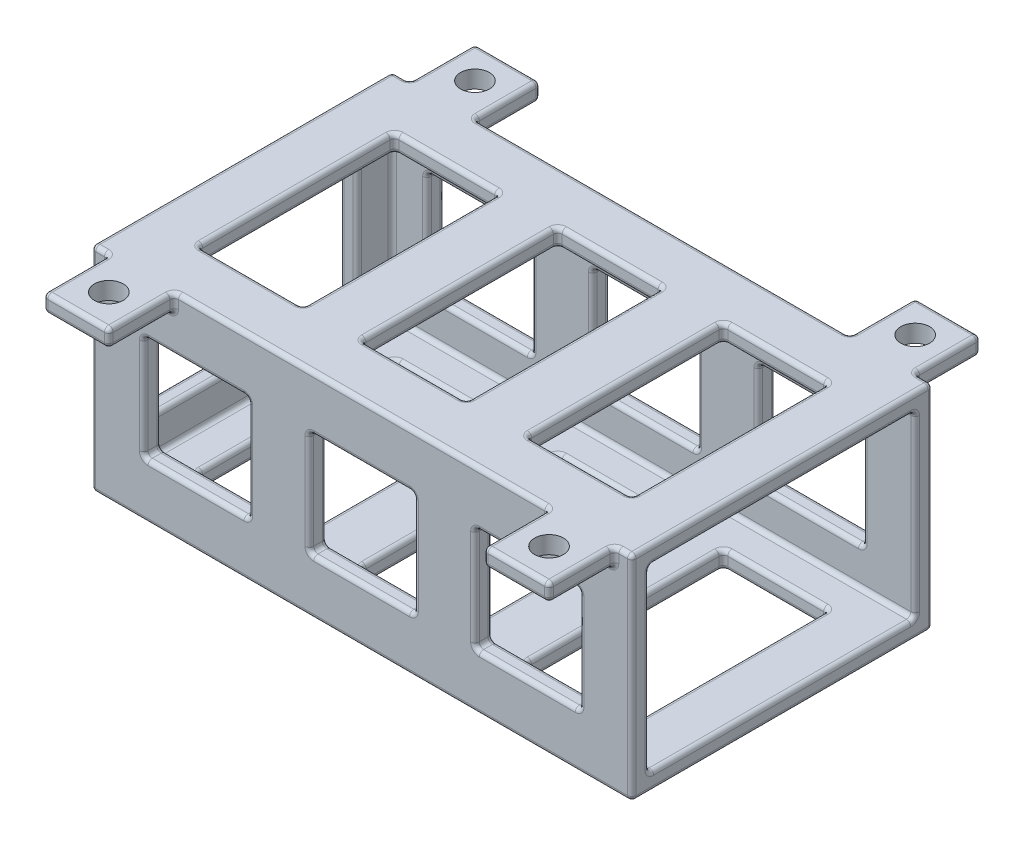
SolidWorks part; units mm, degrees
ref_plane "Front Plane" through (0, 0, 0) normal (0, 0, 1) x (1, 0, 0)
ref_plane "Top Plane" through (0, 0, 0) normal (0, 1, 0) x (1, 0, 0)
ref_plane "Right Plane" through (0, 0, 0) normal (1, 0, 0) x (0, 0, -1)
sketch "Sketch1" plane through (0, 0, 0) normal (1, 0, 0) x (0, 0, -1)
  line L1 (17.25, -12.25) -> (-17.25, -12.25)
  line L2 (17.25, -12.25) -> (17.25, 12.25)
  line L3 (17.25, 12.25) -> (-17.25, 12.25)
  line L4 (-17.25, -12.25) -> (-17.25, 12.25)
  line L5 (17.25, -12.25) -> (-17.25, 12.25) construction
  line L6 (17.25, 12.25) -> (-17.25, -12.25) construction
  point P0 (0, 0)
  dimension "D1" = 34.5
  dimension "D2" = 24.5
extrude "Boss-Extrude1" add sketch "Sketch1" along normal mid plane 62
shell "Shell1" thickness 2
sketch "Sketch2" plane through (0, 12.25, 0) normal (0, 1, 0) x (1, 0, 0)
  line L0 (0, 24.5081) -> (0, -21.4305) construction
  line L1 (-40.6092, 0) -> (35.4298, 0) construction
  line L2 (31, 17.25) -> (-31, 17.25) construction
  line L3 (-29, 17.25) -> (-21.5, 17.25)
  line L4 (-29, 17.25) -> (-29, 24.75)
  line L5 (-29, 24.75) -> (-21.5, 24.75)
  line L6 (-21.5, 17.25) -> (-21.5, 24.75)
  line L7 (-31, 17.25) -> (-31, -17.25) construction
  line L8 (21.5, 17.25) -> (21.5, 24.75)
  line L9 (29, 24.75) -> (21.5, 24.75)
  line L10 (29, 17.25) -> (29, 24.75)
  line L11 (29, 17.25) -> (21.5, 17.25)
  line L12 (29, -17.25) -> (21.5, -17.25)
  line L13 (29, -17.25) -> (29, -24.75)
  line L14 (29, -24.75) -> (21.5, -24.75)
  line L15 (21.5, -17.25) -> (21.5, -24.75)
  line L16 (-21.5, -17.25) -> (-21.5, -24.75)
  line L17 (-29, -24.75) -> (-21.5, -24.75)
  line L18 (-29, -17.25) -> (-29, -24.75)
  line L19 (-29, -17.25) -> (-21.5, -17.25)
  circle A0 centre (-25.25, 21) radius 1.65
  circle A1 centre (25.25, 21) radius 1.65
  circle A2 centre (25.25, -21) radius 1.65
  circle A3 centre (-25.25, -21) radius 1.65
  point P11 (-25.25, 24.75)
  point P30 (-29, 21)
  dimension "D4" = 3.3
  dimension "D1" = 7.5
  dimension "D2" = 7.5
  dimension "D3" = 2
extrude "Boss-Extrude2" add sketch "Sketch2" against normal blind 2
sketch "Sketch5" plane through (0, 0, -17.25) normal (0, 0, -1) x (-1, 0, 0)
  line L8 (-25, -6) -> (-25, 6)
  line L9 (-25, 6) -> (-13, 6)
  line L10 (-13, 6) -> (-13, -6)
  line L11 (-13, -6) -> (-25, -6)
  line L12 (13, -6) -> (13, 6)
  line L13 (13, 6) -> (25, 6)
  line L14 (25, 6) -> (25, -6)
  line L15 (25, -6) -> (13, -6)
  line L16 (-6, -6) -> (-6, 6)
  line L17 (-6, 6) -> (6, 6)
  line L18 (6, 6) -> (6, -6)
  line L19 (6, -6) -> (-6, -6)
  line L21 (31, -12.25) -> (31, 12.25) construction
  line L23 (-31, -12.25) -> (-31, 12.25) construction
  point P24 (-13, 0)
  point P25 (-6, 0)
  point P26 (13, 0)
  point P28 (0, 6)
  dimension "D2" = 6
  dimension "D3" = 6
  dimension "D4" = 12
  dimension "D8" = 12
  dimension "D9" = 12
  dimension "D10" = 12
  dimension "D11" = 12
  dimension "D12" = 12
extrude "Cut-Extrude3" cut sketch "Sketch5" against normal up to surface (34.5 mm away) contours L11 L10 L9 L8 | L19 L18 L17 L16 | L15 L14 L13 L12 up to face at (0, 7.5, 17.25)
sketch "Sketch6" plane through (0, 12.25, 0) normal (0, 1, 0) x (1, 0, 0)
  line L0 (-24.7334, -11.25) -> (-24.7334, 11.25)
  line L1 (-24.7334, 11.25) -> (-12.7334, 11.25)
  line L2 (-12.7334, 11.25) -> (-12.7334, -11.25)
  line L3 (-12.7334, -11.25) -> (-24.7334, -11.25)
  line L4 (13, -11.25) -> (13, 11.25)
  line L5 (13, 11.25) -> (25, 11.25)
  line L6 (25, 11.25) -> (25, -11.25)
  line L7 (25, -11.25) -> (13, -11.25)
  line L8 (-6, -11.25) -> (-6, 11.25)
  line L9 (-6, 11.25) -> (6, 11.25)
  line L10 (6, 11.25) -> (6, -11.25)
  line L11 (6, -11.25) -> (-6, -11.25)
  line L12 (21.5, 17.25) -> (-21.5, 17.25) construction
  line L13 (-31, 17.25) -> (-31, -17.25) construction
  line L14 (31, 17.25) -> (31, -17.25) construction
  point P12 (-12.7334, 0)
  point P13 (-6, 0)
  point P15 (0, 11.25)
  dimension "D1" = 12
  dimension "D2" = 6
  dimension "D3" = 12
  dimension "D4" = 12
  dimension "D5" = 6.2666
  dimension "D6" = 6
extrude "Cut-Extrude4" cut sketch "Sketch6" against normal up to surface (24.5 mm away) up to face at (0, -12.25, 0)
sketch "Sketch7" plane through (-31, 0, 0) normal (-1, 0, 0) x (0, 0, 1)
  line L0 (-11.25, 6.25) -> (-11.25, -6.25)
  line L1 (-11.25, -6.25) -> (11.25, -6.25)
  line L2 (11.25, -6.25) -> (11.25, 6.25)
  line L3 (11.25, 6.25) -> (-11.25, 6.25)
  line L4 (-17.25, -12.25) -> (-17.25, 12.25) construction
  line L5 (-17.25, 12.25) -> (17.25, 12.25) construction
  line L6 (17.25, 12.25) -> (17.25, -12.25) construction
  line L7 (17.25, -12.25) -> (-17.25, -12.25) construction
  dimension "D1" = 6
  dimension "D2" = 6
  dimension "D3" = 6
  dimension "D4" = 6
extrude "Cut-Extrude5" cut sketch "Sketch7" against normal up to surface (2 mm away) up to face at (-29, 0, 0)
fillet "Fillet1" radius 0.5 224 edges at (31, 0, -17.25) (31, -12.25, 0) (31, 0, 17.25) (31, 12.25, 0) (31, 0, -15.25) (31, -10.25, 0) (31, 0, 15.25) (31, 10.25, 0) (0, -12.25, -11.25) (6, -12.25, 0) (0, -12.25, 11.25) (-6, -12.25, 0) (19, -12.25, -11.25) (25, -12.25, 0) (19, -12.25, 11.25) (13, -12.25, 0) (-18.7334, -12.25, -11.25) (-12.7334, -12.25, 0) (-18.7334, -12.25, 11.25) (-24.7334, -12.25, 0) (-29, 12.25, -21) (-29, 10.25, -21) (-25.25, 12.25, -24.75) (-25.25, 10.25, -24.75) (-21.5, 12.25, -21) (-21.5, 10.25, -21) (21.5, 12.25, -21) (21.5, 10.25, -21) (25.25, 12.25, -24.75) (25.25, 10.25, -24.75) (29, 12.25, -21) (29, 10.25, -21) (29, 12.25, 21) (29, 10.25, 21) (25.25, 12.25, 24.75) (25.25, 10.25, 24.75) (21.5, 12.25, 21) (21.5, 10.25, 21) (-21.5, 12.25, 21) (-21.5, 10.25, 21) (-25.25, 12.25, 24.75) (-25.25, 10.25, 24.75) (-29, 12.25, 21) (-29, 10.25, 21) (0, 12.25, -11.25) (-6, 12.25, 0) (0, 12.25, 11.25) (6, 12.25, 0) (19, 12.25, -11.25) (13, 12.25, 0) (19, 12.25, 11.25) (25, 12.25, 0) (-18.7334, 12.25, -11.25) (-24.7334, 12.25, 0) (-18.7334, 12.25, 11.25) (-12.7334, 12.25, 0) (19, 6, -17.25) (25, 0, -17.25) (19, -6, -17.25) (13, 0, -17.25) (-19, 6, -17.25) (-13, 0, -17.25) (-19, -6, -17.25) (-25, 0, -17.25) (-21.5, 11.25, -17.25) (-25.25, 10.25, -17.25) (-29, 11.25, -17.25) (0, -12.25, -17.25) (29, 11.25, -17.25) (25.25, 10.25, -17.25) (21.5, 11.25, -17.25) (0, 12.25, -17.25) (0, 6, -17.25) (6, 0, -17.25) (0, -6, -17.25) (-6, 0, -17.25) (-31, -12.25, 0) (-31, 0, -17.25) (-31, 12.25, 0) (-31, 0, 11.25) (-31, 6.25, 0) (-31, 0, -11.25) (-31, -6.25, 0) (19, -6, 17.25) (25, 0, 17.25) (19, 6, 17.25) (13, 0, 17.25) (-19, -6, 17.25) (-13, 0, 17.25) (-19, 6, 17.25) (-25, 0, 17.25) (21.5, 11.25, 17.25) (25.25, 10.25, 17.25) (29, 11.25, 17.25) (0, -12.25, 17.25) (-31, 0, 17.25) (-29, 11.25, 17.25) (-25.25, 10.25, 17.25) (-21.5, 11.25, 17.25) (0, 12.25, 17.25) (0, -6, 17.25) (6, 0, 17.25) (0, 6, 17.25) (-6, 0, 17.25) (6, -10.25, 0) (0, -10.25, -11.25) (-6, -10.25, 0) (0, -10.25, 11.25) (25, -10.25, 0) (19, -10.25, -11.25) (13, -10.25, 0) (19, -10.25, 11.25) (-12.7334, -10.25, 0) (-18.7334, -10.25, -11.25) (-24.7334, -10.25, 0) (-18.7334, -10.25, 11.25) (25, 0, 15.25) (19, -6, 15.25) (13, 0, 15.25) (19, 6, 15.25) (6, 0, 15.25) (0, -6, 15.25) (-6, 0, 15.25) (0, 6, 15.25) (-13, 0, 15.25) (-19, -6, 15.25) (-25, 0, 15.25) (-19, 6, 15.25) (1, -10.25, 15.25) (25, 0, -15.25) (19, 6, -15.25) (13, 0, -15.25) (19, -6, -15.25) (6, 0, -15.25) (0, 6, -15.25) (-6, 0, -15.25) (0, -6, -15.25) (-13, 0, -15.25) (-19, 6, -15.25) (-25, 0, -15.25) (-19, -6, -15.25) (1, -10.25, -15.25) (1, 10.25, 15.25) (1, 10.25, -15.25) (-6, 10.25, 0) (0, 10.25, -11.25) (6, 10.25, 0) (0, 10.25, 11.25) (13, 10.25, 0) (19, 10.25, -11.25) (25, 10.25, 0) (19, 10.25, 11.25) (-24.7334, 10.25, 0) (-18.7334, 10.25, -11.25) (-12.7334, 10.25, 0) (-18.7334, 10.25, 11.25) (-29, -6.25, 0) (-29, 0, -11.25) (-29, 6.25, 0) (-29, 0, 11.25) (-29, 10.25, 0) (-29, 0, -15.25) (-29, -10.25, 0) (-29, 0, 15.25) (-12.7334, 11.25, 11.25) (-24.7334, 11.25, 11.25) (13, 11.25, 11.25) (-6, 11.25, 11.25) (-24.7334, 11.25, -11.25) (-12.7334, 11.25, -11.25) (-6, 11.25, -11.25) (6, 11.25, -11.25) (6, 11.25, 11.25) (25, 11.25, 11.25) (13, 11.25, -11.25) (25, 11.25, -11.25) (13, -11.25, -11.25) (25, -11.25, -11.25) (13, -11.25, 11.25) (25, -11.25, 11.25) (-6, -11.25, 11.25) (6, -11.25, 11.25) (6, -11.25, -11.25) (-6, -11.25, -11.25) (-12.7334, -11.25, 11.25) (-12.7334, -11.25, -11.25) (-24.7334, -11.25, -11.25) (-24.7334, -11.25, 11.25) (-25, 6, -16.25) (-25, -6, -16.25) (-6, 6, -16.25) (-6, -6, -16.25) (13, 6, -16.25) (13, -6, -16.25) (25, -6, -16.25) (25, 6, -16.25) (6, -6, -16.25) (6, 6, -16.25) (-13, -6, -16.25) (-13, 6, -16.25) (25, 6, 16.25) (25, -6, 16.25) (6, 6, 16.25) (6, -6, 16.25) (-13, 6, 16.25) (-13, -6, 16.25) (-25, -6, 16.25) (-25, 6, 16.25) (-6, -6, 16.25) (-6, 6, 16.25) (13, -6, 16.25) (13, 6, 16.25) (21.5, 11.25, 24.75) (29, 11.25, 24.75) (-21.5, 11.25, 24.75) (-29, 11.25, 24.75) (-29, 11.25, -24.75) (-21.5, 11.25, -24.75) (21.5, 11.25, -24.75) (29, 11.25, -24.75) (-30, 12.25, -17.25) (30, 12.25, -17.25) (30, 12.25, 17.25) (-30, 12.25, 17.25)
